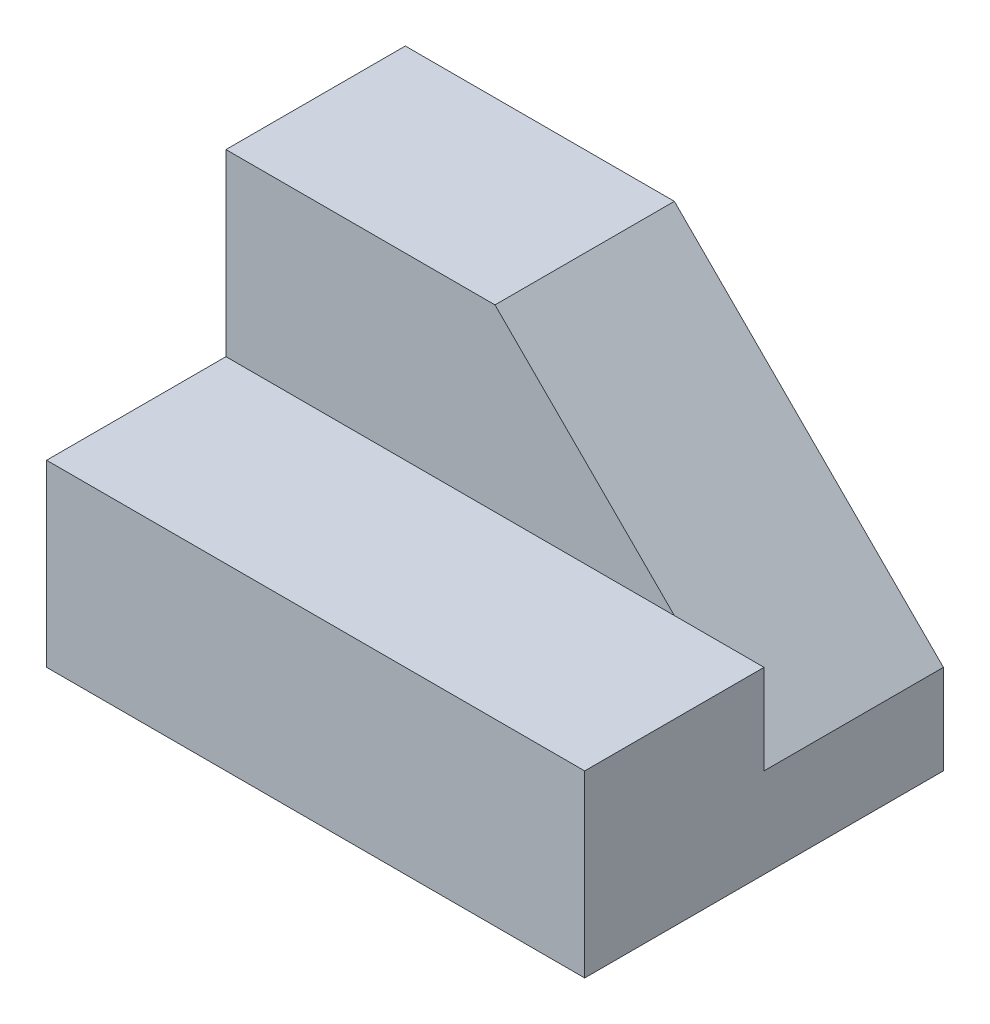
SolidWorks part; units mm, degrees
ref_plane "前基準面" through (0, 0, 0) normal (0, 0, 1) x (1, 0, 0)
ref_plane "上基準面" through (0, 0, 0) normal (0, 1, 0) x (1, 0, 0)
ref_plane "右基準面" through (0, 0, 0) normal (1, 0, 0) x (0, 0, -1)
sketch "草圖1" plane through (0, 0, 0) normal (0, 1, 0) x (1, 0, 0)
  line L1 (-15, 10) -> (15, 10)
  line L2 (-15, 10) -> (-15, -10)
  line L3 (-15, -10) -> (15, -10)
  line L4 (15, 10) -> (15, -10)
  line L5 (-15, 10) -> (15, -10) construction
  line L6 (-15, -10) -> (15, 10) construction
  line L7 (-15, 10) -> (0, 10)
  line L8 (-15, 10) -> (-15, 0)
  line L9 (-15, 0) -> (0, 0)
  line L10 (0, 10) -> (0, 0)
  line L11 (0, 0) -> (15, 0)
  line L12 (0, 0) -> (0, 10)
  line L13 (0, 10) -> (15, 10)
  line L14 (15, 0) -> (15, 10)
  point P0 (0, 0)
  dimension "D1" = 30
  dimension "D2" = 20
  dimension "D3" = 10
  dimension "D4" = 15
extrude "填料-伸長1" add sketch "草圖1" along normal blind 10 contours L10 L1 L2 L9 | L11 L9 L2 L3 L4 | L10 L11 L4 L1 region at (-7.5, 0, -5) region at (7.5, 0, -5) region at (0, 0, 5)
extrude "填料-伸長2" add sketch "草圖1<3>" along normal blind 20 contours L10 L1 L2 L9 | L10 L11 L4 L1 region at (-7.5, 0, -5) region at (7.5, 0, -5)
sketch "草圖1<3>" plane through (0, 0, 0) normal (0, 1, 0) x (1, 0, 0) same geometry as "草圖1"
sketch "草圖2" plane through (0, 0, -10) normal (0, 0, -1) x (-1, 0, 0)
  line L0 (-15, 5) -> (0, 20)
  line L1 (-15, 20) -> (-15, 0) construction
  line L2 (15, 20) -> (-15, 20) construction
  line L3 (0, 20) -> (-15, 20)
  line L4 (-15, 20) -> (-15, 5)
  dimension "D1" = 15
  dimension "D2" = 15
extrude "除料-伸長1" cut sketch "草圖2" against normal blind 10
scale "縮放比例1" scale about centroid uniform scaling yes scale factor 0.2
